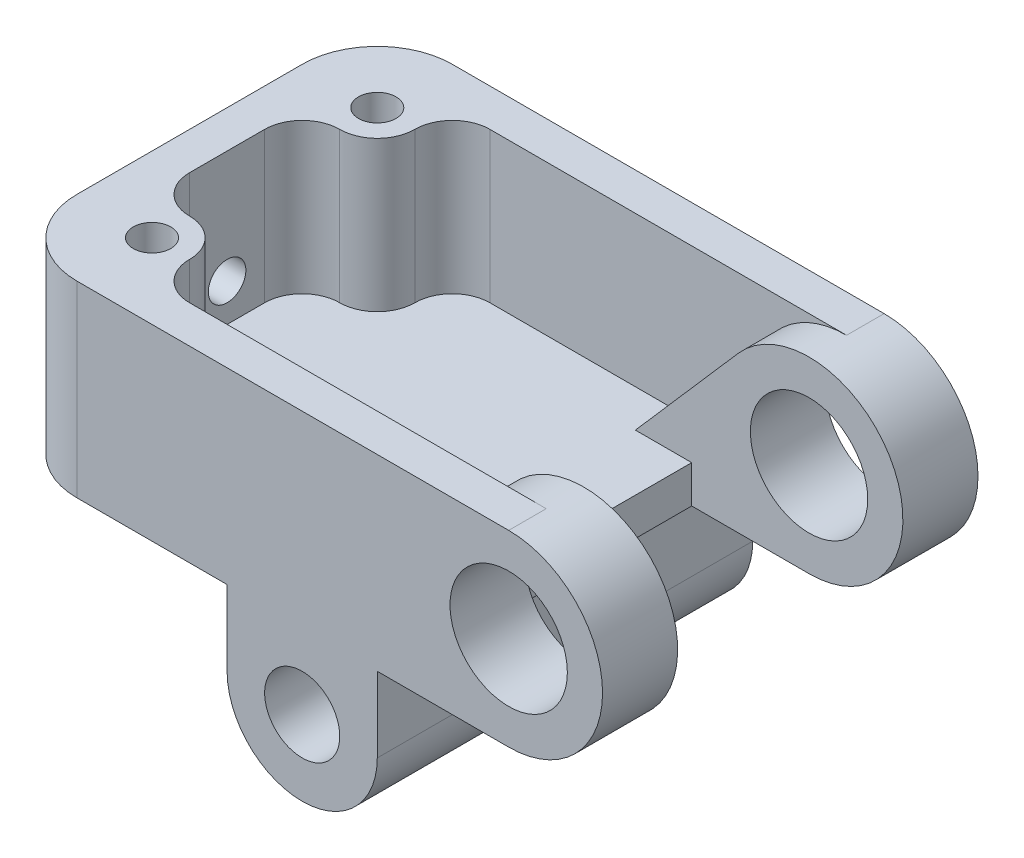
SolidWorks part; units mm, degrees
ref_plane "Front Plane" through (0, 0, 0) normal (0, 0, 1) x (1, 0, 0)
ref_plane "Top Plane" through (0, 0, 0) normal (0, 1, 0) x (1, 0, 0)
ref_plane "Right Plane" through (0, 0, 0) normal (1, 0, 0) x (0, 0, -1)
sketch "Sketch1" plane through (0, 0, 0) normal (0, 0, 1) x (1, 0, 0)
  line L0 (48, -16) -> (48, 0)
  line L1 (0, 0) -> (48, 0)
  line L2 (0, 0) -> (0, 40)
  line L3 (0, 40) -> (128, 40)
  line L4 (128, 0) -> (128, 40)
  line L6 (80, 0) -> (80, -16)
  line L7 (64, 40) -> (64, -16) construction
  line L8 (80, 0) -> (128, 0)
  arc A0 (48, -16) -> (80, -16) centre (64, -16) ccw
  circle A1 centre (64, -16) radius 8
  dimension "D3" = 32
  dimension "D4" = 16
  dimension "D1" = 128
  dimension "D2" = 40
  dimension "D5" = 16
extrude "Boss-Extrude1" add sketch "Sketch1" along normal mid plane 80
sketch "Sketch2" plane through (0, 40, 0) normal (0, 1, 0) x (1, 0, 0)
  line L0 (128, -40) -> (128, 40) construction
  line L1 (128, 32) -> (83, 32)
  line L2 (128, 32) -> (128, -32)
  line L3 (128, -32) -> (83, -32)
  line L4 (83, 32) -> (83, -32)
  line L5 (128, 40) -> (0, 40) construction
  line L6 (128, -40) -> (0, -40) construction
  dimension "D1" = 8
  dimension "D2" = 8
  dimension "D3" = 45
extrude "Cut-Extrude1" cut sketch "Sketch2" against normal blind 80
fillet "Fillet1" radius 20 4 edges at (128, 0, 36) (128, 0, -36) (128, 40, -36) (128, 40, 36)
hole_wizard "Hole1" positions "Sketch3" profile "Sketch4" legacy end condition through all
sketch "Sketch3" plane through (0, 0, 40) normal (0, 0, 1) x (1, 0, 0)
  point P0 (108, 20)
sketch "Sketch4" plane through (108, 20, 40) normal (1, 0, 0) x (0, -1, 0)
  line L0 (0, 0) -> (0, 80)
  line L1 (0, 80) -> (12.5, 80)
  line L2 (12.5, 80) -> (12.5, 0)
  line L3 (12.5, 0) -> (0, 0)
  line L4 (0, 110) -> (0, -10) construction
  dimension "Diameter" = 25
  dimension "Depth" = 80
fillet "Fillet2" radius 16 2 edges at (0, 20, -40) (0, 20, 40)
hole_wizard "Hole2" positions "Sketch5" profile "Sketch6" legacy end condition through all
sketch "Sketch5" plane through (0, 40, 0) normal (0, 1, 0) x (1, 0, 0)
  point P0 (16, 24)
  point P3 (16, -24)
sketch "Sketch6" plane through (16, 40, -24) normal (1, 0, 0) x (0, 0, 1)
  line L0 (0, 0) -> (0, 72)
  line L1 (0, 72) -> (4, 72)
  line L2 (4, 72) -> (4, 0)
  line L3 (4, 0) -> (0, 0)
  line L4 (0, 110) -> (0, -10) construction
  dimension "Diameter" = 8
  dimension "Depth" = 72
sketch "Sketch7" plane through (0, 40, 0) normal (0, 1, 0) x (1, 0, 0)
  line L2 (8, -24) -> (8, 24)
  line L3 (8, -8) -> (8, 8)
  line L5 (108, 32) -> (16, 32)
  line L6 (83, 32) -> (32, 32)
  line L7 (83, 32) -> (83, -32) construction
  line L8 (108, -32) -> (16, -32)
  line L9 (83, -32) -> (32, -32)
  line L10 (83, 32) -> (83, -32)
  arc A0 (16, 16) -> (24, 24) centre (16, 24) ccw
  arc A1 (24, -24) -> (16, -16) centre (16, -24) ccw
  arc A2 (8, -8) -> (16, -16) centre (16, -8) ccw
  arc A3 (16, 16) -> (8, 8) centre (16, 8) ccw
  arc A4 (24, 24) -> (32, 32) centre (32, 24) cw
  arc A5 (24, -24) -> (32, -32) centre (32, -24) ccw
  point P1 (-43.71, 30.1395)
  dimension "D1" = 8
  dimension "D5" = 8
  dimension "D2" = 8
  dimension "D3" = 8
  dimension "D4" = 8
extrude "Cut-Extrude2" cut sketch "Sketch7" against normal blind 32
sketch "Sketch8" plane through (0, 0, -32) normal (0, 0, 1) x (1, 0, 0)
  line L0 (83, 8) -> (32, 8) construction
  line L1 (83, 0) -> (83, 8) construction
  line L2 (108, 0) -> (83, 0) construction
  line L3 (83, 8) -> (71, 8)
  line L4 (83, 0) -> (83, 8)
  line L5 (108, 0) -> (83, 0)
  line L6 (71, 8) -> (92.9261, 33.1445)
  circle A2 centre (108, 20) radius 12.5 construction
  arc A4 (108, 0) -> (92.9261, 33.1445) centre (108, 20) ccw
  circle A5 centre (108, 20) radius 12.5
  arc A6 (108, 0) -> (128, 20) centre (108, 20) ccw construction
  dimension "D1" = 12
extrude "Boss-Extrude2" add sketch "Sketch8" along normal blind 8
mirror "Mirror1" about plane through (0, 0, 0) normal (0, 0, 1) of "Boss-Extrude2"
sketch "Sketch9" plane through (0, 0, 0) normal (-1, 0, 0) x (0, 0, 1)
  line L0 (-16, 16) -> (-16, 0)
  line L1 (24, 0) -> (-24, 0) construction
  line L2 (-16, 0) -> (16, 0)
  line L3 (16, 0) -> (16, 16)
  arc A0 (16, 16) -> (-16, 16) centre (0, 16) ccw
  dimension "D1" = 32
  dimension "D2" = 16
extrude "Boss-Extrude3" add sketch "Sketch9" along normal blind 8
hole_wizard "Hole3" positions "Sketch10" profile "Sketch11" legacy end condition through all
sketch "Sketch10" plane through (-8, 0, 0) normal (-1, 0, 0) x (0, 0, 1)
  point P0 (0, 16)
  point P4 (0, 0)
sketch "Sketch11" plane through (-8, 16, 0) normal (0, 1, 0) x (0, 0, 1)
  line L0 (0, 0) -> (0, 136)
  line L1 (0, 136) -> (4, 136)
  line L2 (4, 136) -> (4, 0)
  line L3 (4, 0) -> (0, 0)
  line L4 (0, 110) -> (0, -10) construction
  dimension "Diameter" = 8
  dimension "Depth" = 136
